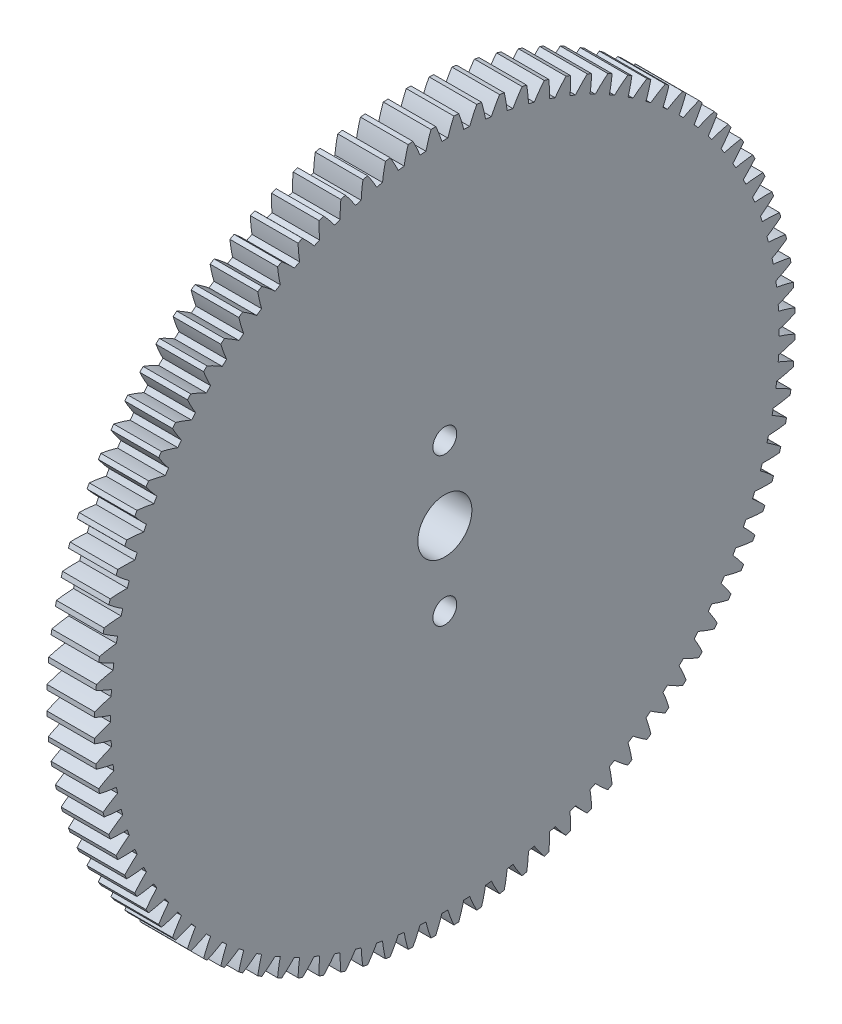
SolidWorks part; units mm, degrees
ref_plane "Plane1" through (0, 0, 0) normal (0, 0, 1) x (1, 0, 0)
ref_plane "Plane2" through (0, 0, 0) normal (0, 1, 0) x (1, 0, 0)
ref_plane "Plane3" through (0, 0, 0) normal (1, 0, 0) x (0, 0, -1)
sketch "HoldingSke" plane through (0, 0, 0) normal (0, 1, 0) x (1, 0, 0)
  line L0 (0, 0) -> (-0.1161, -1.105)
  line L1 (-15, 0) -> (100, 0) construction
  line L2 (0, 0) -> (-2.1039, 2.3779)
  line L3 (0, 0) -> (-11.863, 4.5341)
  line L4 (0, 0) -> (-0.9027, 8.5887)
  line L5 (0, 0) -> (-46.8476, -17.4728)
  line L6 (0, 0) -> (-1.6579, -1.1186)
  line L7 (-2.1039, 2.3779) -> (8.6586, 51.2059)
  line L8 (-76.2, 54.61) -> (-76.1, 54.61)
  line L9 (-71.009, 38.7566) -> (-53.1078, 45.2721)
  line L10 (-76.2, 71.12) -> (104.1128, 71.12)
  line L11 (0, 0) -> (-2, 0)
  line L12 (-76.2, 101.6) -> (-76.166, 101.6)
  line L13 (24.9733, 27.94) -> (52.9518, 28.4284)
  line L14 (24.9733, 27.94) -> (24.9743, 27.94)
  line L15 (24.9733, 27.94) -> (100.4006, 29.5858)
  line L16 (-63.627, -0.9) -> (-12.827, -0.9)
  circle A0 centre (0, 0) radius 0.5
  circle A1 centre (0, 0) radius 37.5
  circle A2 centre (0, 0) radius 37.5
  circle A3 centre (0, 0) radius 0.5
  dimension "MHD" = 75
  dimension "Hub_dia" = 75
  dimension "Bore" = 1
  dimension "MBD" = 1
  dimension "Num_teeth" = 96
  dimension "Pitch" = 1.1111
  dimension "Overall_len" = 50
  dimension "Show_teeth" = 96
  dimension "Thickness" = 2
  dimension "OAL" = 50.0001
  dimension "T_dim" = 0.1
  dimension "Ap" = 20
  dimension "H" = 19.05
  dimension "Pitch_radius" = 180.3128
  dimension "Width" = 2
  dimension "Backlash" = 0.034
  dimension "Addendum_fac" = 1
  dimension "Dedendum_fac" = 1.25
  dimension "Clearance_fac" = 0.25
  dimension "Dedendum_add" = 0.001
  dimension "Module" = 0.9
sketch "BasProSke" plane through (0, 0, 0) normal (0, 1, 0) x (1, 0, 0)
  line L0 (-10, 0) -> (60, 0) construction
  line L1 (0, 0) -> (0, 44.1)
  line L2 (0, 0) -> (2, 0)
  line L3 (2, 0) -> (2, 44.1)
  line L4 (2, 44.1) -> (0, 44.1)
  dimension "Thickness" = 2
  dimension "Diameter" = 88.2
revolve "Base-Revolve" add sketch "BasProSke" angle 360 about L0
sketch "TooCutSke" plane through (0, 0, 0) normal (1, 0, 0) x (0, 0, -1)
  line L1 (0, 0) -> (0, 107) construction
  line L2 (0, 0) -> (-0.7663, 43.1932) construction
  line L3 (0, 0) -> (-2.8266, 86.344) construction
  line L4 (-0.7663, 43.1932) -> (-1.4133, 43.172) construction
  arc A0 (0.3737, 42.0723) -> (-0.3737, 42.0723) centre (0, 0) ccw
  arc A1 (1.1542, 44.1103) -> (-1.1542, 44.1103) centre (0, 0) ccw
  circle A2 centre (0, 0) radius 43.2 construction
  circle A3 centre (0, 0) radius 40.5947 construction
  arc A4 (-0.3737, 42.0723) -> (-1.1542, 44.1103) centre (-16.8689, 36.9239) ccw
  arc A5 (1.1542, 44.1103) -> (0.3737, 42.0723) centre (16.8689, 36.9239) ccw
  dimension "Root_dia" = 84.148
  dimension "Overcut_dia" = 88.2508
  dimension "Pitch_dia" = 86.4
  dimension "Base_dia" = 81.1894
  dimension "Flank_rad" = 17.28
  dimension "Half_ang" = 1.875
  dimension "Half_CT" = 0.6473
extrude "ToothCut" cut sketch "TooCutSke" along normal through all
fillet "Breaks" [suppressed] radius 0.018 tangent propagation no
fillet "RootFillets" [suppressed] radius 0.226
pattern_circular "TeethCuts" count 96 every 3.75 about axis through (-10, 0, 0) along (1, 0, 0) of "ToothCut", "RootFillets", "Breaks"
sketch "HubNeaOneSke" plane through (0, 0, 0) normal (-1, 0, 0) x (0, 0, 1)
  circle A0 centre (0, 0) radius 37.5
  dimension "Diameter" = 75
extrude "HubNearOne" [suppressed] add sketch "HubNeaOneSke" along normal blind 48.0001
sketch "HubNeaBotSke" plane through (0, 0, 0) normal (-1, 0, 0) x (0, 0, 1)
  circle A0 centre (0, 0) radius 37.5
  dimension "Diameter" = 75
extrude "HubNearBoth" [suppressed] add sketch "HubNeaBotSke" along normal blind 24
ref_plane "FarPln" through (2, 0, 0) normal (1, 0, 0) x (0, 0, -1)
sketch "HubFarSke" plane through (2, 0, 0) normal (1, 0, 0) x (0, 0, -1)
  circle A0 centre (0, 0) radius 37.5
  dimension "Diameter" = 75
extrude "HubFar" [suppressed] add sketch "HubFarSke" along normal blind 24
sketch "BorSke" plane through (0, 0, 0) normal (1, 0, 0) x (0, 0, -1)
  line L0 (-1000, 0) -> (49000, 0) construction
  circle A0 centre (0, 0) radius 3.4
  circle A1 centre (0, -9.3) radius 1.5
  circle A2 centre (0, 9.3) radius 1.5
  dimension "D1" = 3
  dimension "Diameter" = 6.8
  dimension "D2" = 9.3
extrude "Bore" cut sketch "BorSke" along normal mid plane 100.0001
sketch "KeySke" plane through (0, 0, 0) normal (1, 0, 0) x (0, 0, -1)
  line L0 (-0.05, 0) -> (-0.05, 0.6)
  line L1 (-0.05, 0.6) -> (0.05, 0.6)
  line L2 (0.05, 0.6) -> (0.05, 0)
  line L3 (0, 0) -> (0, 34) construction
  line L4 (-0.05, 0) -> (0.05, 0)
  dimension "Offset" = 0.6
extrude "Keyway" [suppressed] cut sketch "KeySke" along normal mid plane 100.0001
pattern_circular "Keyway2" [suppressed] count 2 every 90 about axis through (-10, 0, 0) along (1, 0, 0) reverse direction yes
scale "Scale1" scale about centroid uniform scaling no x scale factor 3 y scale factor 1 z scale factor 1
equation "' \"Module@HoldingSke\" = 6.35"
equation "' \"Num_teeth@HoldingSke\" = 12"
equation "' \"Ap@HoldingSke\" =  20"
equation "' \"Ap@HoldingSke\" = 20"
equation "' \"Width@HoldingSke\" = 0.5 * 25.4"
equation "' \"Hub_dia@HoldingSke\"= 1 * 25.4"
equation "' \"Hub_dia@HoldingSke\" = 1 * 25.4"
equation "' \"Overall_len@HoldingSke\" = 1.0 * 25.4"
equation "' \"Bore@HoldingSke\" = 0.75 * 25.4"
equation "' \"T_dim@HoldingSke\" = 0.1 * 25.4"
equation "' \"Width@KeySke\" = 0.25 * 25.4"
equation "' \"Show_teeth@HoldingSke\" = 13"
equation "' \"Backlash@HoldingSke\" = 0.009 * 25.4"
equation "' \"Addendum_fac@HoldingSke\" = 1.0"
equation "' \"Dedendum_fac@HoldingSke\" = 1.25"
equation "' \"Dedendum_add@HoldingSke\" = 0.00005 * 25.4"
equation "' \"Clearance_fac@HoldingSke\" = 0.25"
equation "\"Pitch@HoldingSke\" = 1 / \"Module@HoldingSke\""
equation "\"Overcut_dia@TooCutSke\" = (\"Num_teeth@HoldingSke\" + 2 * \"Addendum_fac@HoldingSke\") / \"Pitch@HoldingSke\" + 0.002 * 25.4"
equation "\"Pitch_dia@TooCutSke\" = \"Num_teeth@HoldingSke\" / \"Pitch@HoldingSke\""
equation "\"Base_dia@TooCutSke\" = \"Num_teeth@HoldingSke\" / \"Pitch@HoldingSke\" * cos((\"Ap@HoldingSke\"  * 3.14159265 / 180))"
equation "\"Root_dia@TooCutSke\" = (\"Num_teeth@HoldingSke\" + 2) / \"Pitch@HoldingSke\" - 2 * (\"Addendum_fac@HoldingSke\" + \"Dedendum_fac@HoldingSke\") / \"Pitch@HoldingSke\" - \"Dedendum_add@HoldingSke\" * 2"
equation "\"Half_ang@TooCutSke\" = 180 / \"Num_teeth@HoldingSke\""
equation "\"Half_CT@TooCutSke\" = \"Num_teeth@HoldingSke\" / \"Pitch@HoldingSke\" * sin((3.14159265 / 2 / \"Num_teeth@HoldingSke\")) / 2 - 7 * \"Backlash@HoldingSke\" / 4"
equation "\"Flank_rad@TooCutSke\" = \"Num_teeth@HoldingSke\" / \"Pitch@HoldingSke\" / 5"
equation "\"Radius@RootFillets\" = \"Clearance_fac@HoldingSke\" / \"Pitch@HoldingSke\" + \"Dedendum_add@HoldingSke\""
equation "\"Break_rad@Breaks\" = 0.02 / \"Pitch@HoldingSke\""
equation "\"Thickness@HoldingSke\" = \"Width@HoldingSke\""
equation "\"OAL@HoldingSke\" = \"Thickness@HoldingSke\""
equation "\"MHD@HoldingSke\" = (\"Num_teeth@HoldingSke\" + 2) / \"Pitch@HoldingSke\" - 2 * (\"Addendum_fac@HoldingSke\" + \"Dedendum_fac@HoldingSke\")  / \"Pitch@HoldingSke\" - \"Dedendum_add@HoldingSke\" * 2"
equation "\"MBD@HoldingSke\" = (\"Num_teeth@HoldingSke\" + 2) / \"Pitch@HoldingSke\" - 2 * (\"Addendum_fac@HoldingSke\" + \"Dedendum_fac@HoldingSke\")  / \"Pitch@HoldingSke\" - \"Dedendum_add@HoldingSke\" * 2 - 0.002 * 25.4"
equation "\"MHD@HoldingSke\" = ((sgn( \"MHD@HoldingSke\" - \"Hub_dia@HoldingSke\" )-1)*( \"MHD@HoldingSke\" - \"Hub_dia@HoldingSke\" ))/-2+ \"Hub_dia@HoldingSke\""
equation "\"MBD@HoldingSke\" = ((sgn( \"MBD@HoldingSke\" - \"Bore@HoldingSke\" )-1)*( \"MBD@HoldingSke\" - \"Bore@HoldingSke\" ))/-2+ \"Bore@HoldingSke\""
equation "\"OAL@HoldingSke\" = ((sgn( \"OAL@HoldingSke\" - \"Overall_len@HoldingSke\" )+1)*( \"OAL@HoldingSke\" - \"Overall_len@HoldingSke\" ))/2 + \"Overall_len@HoldingSke\" + 0.000002 * 25.4"
equation "\"Num_teeth@TeethCuts\" = int( \"Show_teeth@HoldingSke\" ) + 1"
equation "\"Num_teeth@TeethCuts\" = ((sgn( \"Num_teeth@TeethCuts\" - \"Num_teeth@HoldingSke\" )-1)*( \"Num_teeth@TeethCuts\" - \"Num_teeth@HoldingSke\" ))/-2+ \"Num_teeth@HoldingSke\""
equation "\"Num_teeth@TeethCuts\" = ((sgn( \"Num_teeth@TeethCuts\" - 2.0)+1)*( \"Num_teeth@TeethCuts\" - 2.0))/2 +2.0"
equation "\"Angle@TeethCuts\" = 360.0 / \"Num_teeth@HoldingSke\""
equation "\"Diameter@BasProSke\" = (\"Num_teeth@HoldingSke\" + 2 * \"Addendum_fac@HoldingSke\") / \"Pitch@HoldingSke\""
equation "\"Thickness@BasProSke\"  = \"Thickness@HoldingSke\""
equation "' \"Fillet_rad@BasProSke\" =  \"Thickness@HoldingSke\" * 0.05"
equation "' \"Fillet_rad@BasProSke\" = \"Thickness@HoldingSke\" * 0.05"
equation "\"MHD@HoldingSke\" = ((sgn( \"MHD@HoldingSke\" - \"Root_dia@TooCutSke\" )-1)*( \"MHD@HoldingSke\" - \"Root_dia@TooCutSke\" ))/-2+ \"Root_dia@TooCutSke\""
equation "\"Diameter@HubNeaOneSke\" = \"MHD@HoldingSke\""
equation "\"Length@HubNearOne\" = \"OAL@HoldingSke\" - \"Thickness@BasProSke\""
equation "\"Diameter@HubNeaBotSke\" = \"MHD@HoldingSke\""
equation "\"Length@HubNearBoth\" = ( \"OAL@HoldingSke\" - \"Thickness@BasProSke\" ) / 2.0"
equation "\"Thickness@FarPln\" = \"Thickness@BasProSke\""
equation "\"Diameter@HubFarSke\" = \"MHD@HoldingSke\""
equation "\"Length@HubFar\" = ( \"OAL@HoldingSke\" - \"Thickness@BasProSke\" ) / 2.0"
equation "\"D1@Bore\" = \"OAL@HoldingSke\" * 2.0"
equation "\"D1@Keyway\" = \"OAL@HoldingSke\" * 2.0"
equation "\"Offset@KeySke\" = \"T_dim@HoldingSke\" + \"MBD@HoldingSke\" / 2.0"
